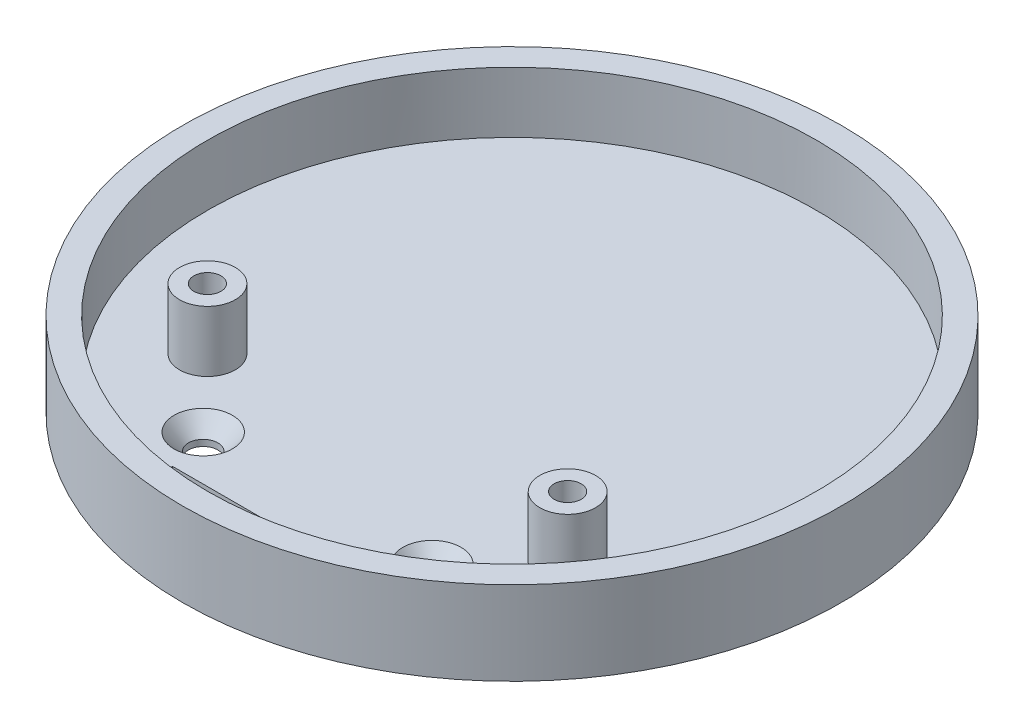
SolidWorks part; units mm, degrees
ref_plane "Front Plane" through (0, 0, 0) normal (0, 0, 1) x (1, 0, 0)
ref_plane "Top Plane" through (0, 0, 0) normal (0, 1, 0) x (1, 0, 0)
ref_plane "Right Plane" through (0, 0, 0) normal (1, 0, 0) x (0, 0, -1)
sketch "Sketch1" plane through (0, 0, 0) normal (0, 1, 0) x (1, 0, 0)
  line L0 (0, 0) -> (0, -29.7612) construction
  line L1 (-11.1125, -26.5862) -> (11.1125, -26.5862)
  line L2 (-11.1125, -26.5862) -> (-11.1125, -32.9362)
  line L3 (-11.1125, -32.9362) -> (11.1125, -32.9362)
  line L4 (11.1125, -26.5862) -> (11.1125, -32.9362)
  line L5 (11.1125, -26.5862) -> (-11.1125, -32.9362) construction
  line L6 (-20, -13.8201) -> (20, -13.8201) construction
  line L7 (-12.7, -21.59) -> (12.7, -21.59)
  circle A0 centre (0, 0) radius 35.3949
  circle A1 centre (0, 0) radius 33.7949
  circle A2 centre (-20, -13.8201) radius 1.5
  circle A3 centre (20, -13.8201) radius 1.5
  circle A4 centre (0, 0) radius 36.5949
  circle A5 centre (-20, -13.8201) radius 3.1
  circle A6 centre (20, -13.8201) radius 3.1
  point P13 (0, -13.8201)
  point P19 (0, -21.59)
  dimension "D1" = 70.7898
  dimension "D2" = 1.6
  dimension "D7" = 3
  dimension "D9" = 1.2
  dimension "D10" = 1.6
  dimension "D3" = 22.225
  dimension "D4" = 6.35
  dimension "D5" = 29.7612
  dimension "D6" = 40
  dimension "D8" = 13.8201
  dimension "D11" = 25.4
  dimension "D12" = 21.59
sketch "Sketch2" plane through (0, 0, 0) normal (0, 1, 0) x (1, 0, 0)
  line L0 (11.1125, -26.5862) -> (11.1125, -32.9362) construction
  line L1 (-11.1125, -26.5862) -> (11.1125, -26.5862) construction
  line L2 (-11.1125, -26.5862) -> (-11.1125, -32.9362) construction
  line L3 (-11.1125, -32.9362) -> (11.1125, -32.9362) construction
  line L4 (11.1125, -26.5862) -> (11.1125, -32.9362)
  line L5 (-11.1125, -26.5862) -> (11.1125, -26.5862)
  line L6 (-11.1125, -26.5862) -> (-11.1125, -32.9362)
  line L7 (-11.1125, -32.9362) -> (11.1125, -32.9362)
  circle A2 centre (0, 0) radius 36.5949 construction
  circle A3 centre (0, 0) radius 36.5949
extrude "Boss-Extrude2" add sketch "Sketch2" along normal blind 2.54
sketch "Sketch3" plane through (0, 2.54, 0) normal (0, 1, 0) x (1, 0, 0)
  circle A0 centre (0, 0) radius 36.5949 construction
  circle A2 centre (0, 0) radius 36.5949
  circle A4 centre (0, 0) radius 33.7949 construction
  circle A5 centre (0, 0) radius 33.7949
extrude "Boss-Extrude3" add sketch "Sketch3" along normal blind 6.75
sketch "Sketch5" plane through (0, 2.54, 0) normal (0, 1, 0) x (1, 0, 0)
  circle A4 centre (-20, -13.8201) radius 3.1 construction
  circle A5 centre (20, -13.8201) radius 3.1 construction
  circle A6 centre (-20, -13.8201) radius 3.1
  circle A7 centre (20, -13.8201) radius 3.1
extrude "Fastener Stand Offs" add sketch "Sketch5" along normal up to surface (6.75 mm away) up to face at (0, 9.29, 36.5949)
sketch "Sketch6" plane through (0, 9.29, 0) normal (0, 1, 0) x (1, 0, 0)
  circle A0 centre (20, -13.8201) radius 1.5 construction
  circle A1 centre (-20, -13.8201) radius 1.5 construction
  circle A2 centre (20, -13.8201) radius 1.5
  circle A3 centre (-20, -13.8201) radius 1.5
extrude "Threaded Insert" cut sketch "Sketch6" against normal through all
hole_wizard "CSK for #4 Flat Head Machine Screw1" positions "Sketch7" profile "Sketch8" countersink size "#4" standard "ANSI Inch" end condition up to next
sketch "Sketch7" plane through (0, 2.54, 0) normal (0, 1, 0) x (1, 0, 0)
  point P0 (-12.7, -21.59)
  point P3 (12.7, -21.59)
sketch "Sketch8" plane through (-12.7, 2.54, 21.59) normal (1, 0, 0) x (0, 0, 1)
  line L0 (0, 0) -> (0, 2.54)
  line L1 (0, 2.54) -> (1.6319, 2.54)
  line L2 (1.6319, 2.54) -> (1.6319, 1.8481)
  line L3 (1.6319, 1.8481) -> (3.2385, 0)
  line L5 (3.2385, 0) -> (0, 0)
  line L6 (-1.6319, 1.8481) -> (-3.2385, 0) construction
  line L11 (0, -6.35) -> (0, 107.95) construction
  dimension "Thru Hole Dia." = 3.2639
  dimension "Thru Hole Depth" = 2.54
  dimension "Near C'Sink Dia." = 6.477
  dimension "Near C'Sink Angle" = 82
